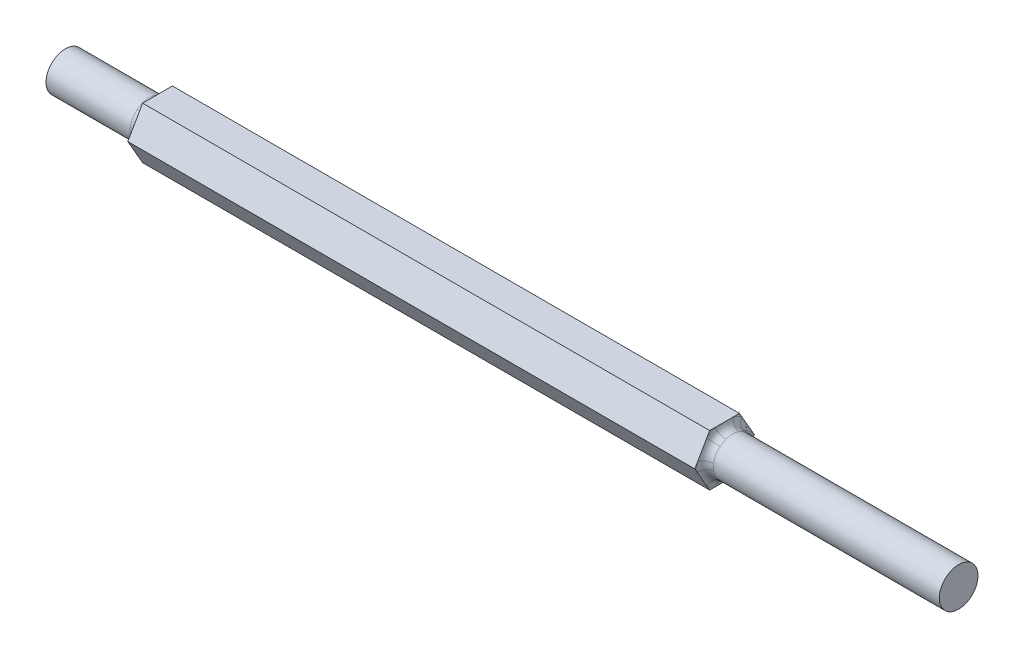
SolidWorks part; units mm, degrees
material "1060 Alloy"
ref_plane "Front Plane" through (0, 0, 0) normal (0, 0, 1) x (1, 0, 0)
ref_plane "Top Plane" through (0, 0, 0) normal (0, 1, 0) x (1, 0, 0)
ref_plane "Right Plane" through (0, 0, 0) normal (1, 0, 0) x (0, 0, -1)
sketch "Sketch1" plane through (0, 0, 0) normal (1, 0, 0) x (0, 0, -1)
  line L1 (3.6662, 0) -> (1.8331, 3.175)
  line L2 (1.8331, 3.175) -> (-1.8331, 3.175)
  line L3 (-1.8331, 3.175) -> (-3.6662, 0)
  line L4 (-3.6662, 0) -> (-1.8331, -3.175)
  line L5 (-1.8331, -3.175) -> (1.8331, -3.175)
  line L6 (1.8331, -3.175) -> (3.6662, 0)
  circle A0 centre (0, 0) radius 3.175 construction
  dimension "D1" = 6.35
extrude "Boss-Extrude1" add sketch "Sketch1" along normal blind 110
sketch "Sketch2" plane through (110, 0, 0) normal (1, 0, 0) x (0, 0, -1)
  circle A0 centre (0, 0) radius 2.3813
  dimension "D1" = 4.7625
extrude "Cut-Extrude1" cut sketch "Sketch2" against normal blind 28.8252 flip side to cut contours A0 | A0 region at (110, 0, 0)
fillet "Fillet1" radius 1 1 edges at (81.1748, 0, -2.3813)
sketch "Sketch3" plane through (0, 0, 0) normal (-1, 0, 0) x (0, 0, 1)
  circle A0 centre (0, 0) radius 2.3813
  dimension "D1" = 4.7625
extrude "Cut-Extrude2" cut sketch "Sketch3" against normal blind 11.35 flip side to cut
fillet "Fillet2" radius 1 1 edges at (11.35, 0, 2.3813)
equation "\"D1@Sketch3\"=\"D1@Sketch2\""
equation "\"BARRING_LNG\"= 1 / 4"
equation "\"PULLY_LNG\"= .688"
equation "\"D1@Cut-Extrude1\"=\"BARRING_LNG\"+\"PULLY_LNG\"+5mm"
equation "\"D1@Cut-Extrude2\"=\"BARRING_LNG\"+5mm"
